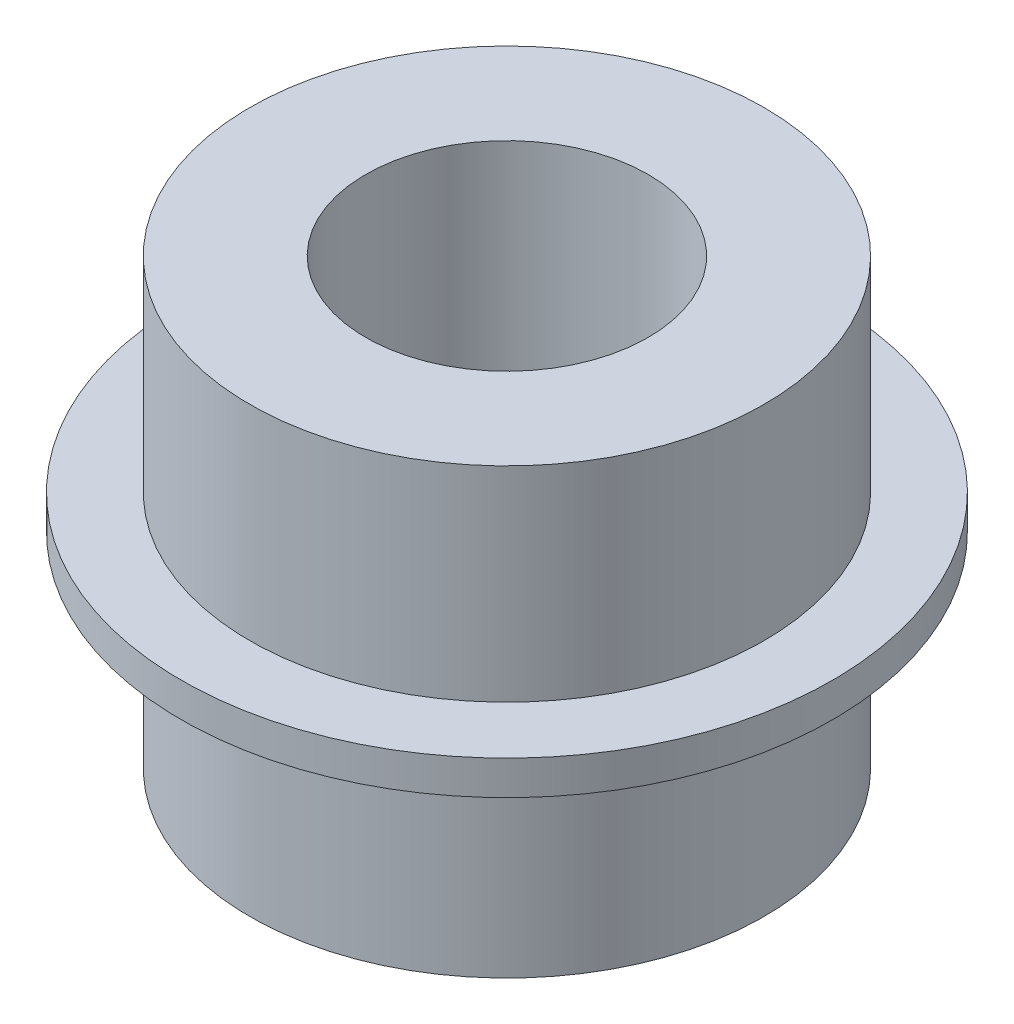
SolidWorks part; units mm, degrees
ref_plane "Front Plane" through (0, 0, 0) normal (0, 0, 1) x (1, 0, 0)
ref_plane "Top Plane" through (0, 0, 0) normal (0, 1, 0) x (1, 0, 0)
ref_plane "Right Plane" through (0, 0, 0) normal (1, 0, 0) x (0, 0, -1)
sketch "Sketch1" plane through (0, 0, 0) normal (0, 0, 1) x (1, 0, 0)
  line L0 (-4.125, -6.477) -> (-4.125, 6.477)
  line L13 (-4.125, 6.477) -> (-7.51, 6.477)
  line L14 (-7.51, 6.477) -> (-7.51, 0.5)
  line L15 (-7.51, 0.5) -> (-9.51, 0.5)
  line L16 (-9.51, 0.5) -> (-9.51, -0.5)
  line L17 (-9.51, -0.5) -> (-7.51, -0.5)
  line L18 (-7.51, -0.5) -> (-7.51, -6.477)
  line L19 (-7.51, -6.477) -> (-4.125, -6.477)
  line L20 (0, 0) -> (0, 9.5041) construction
  point P10 (-4.125, 0)
  dimension "D1" = 4.125
  dimension "D2" = 7.51
  dimension "D3" = 1
  dimension "D4" = 12.954
  dimension "D5" = 2
revolve "Revolve1" add sketch "Sketch1" angle 360 about L20
move or copy body "Body-Convert to Mesh Body1" [suppressed] bodies to move or copy 101 copy no translate (0, 0, 0)
